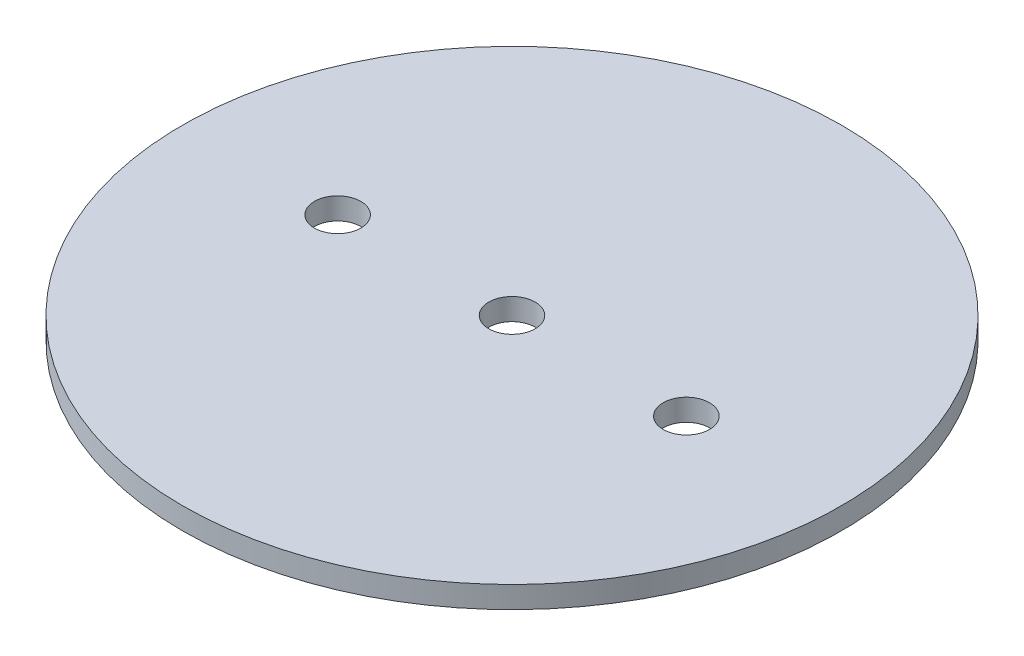
SolidWorks part; units mm, degrees
material "A-Glass Fiber"
ref_plane "Front Plane" through (0, 0, 0) normal (0, 0, 1) x (1, 0, 0)
ref_plane "Top Plane" through (0, 0, 0) normal (0, 1, 0) x (1, 0, 0)
ref_plane "Right Plane" through (0, 0, 0) normal (1, 0, 0) x (0, 0, -1)
sketch "Sketch1" plane through (0, 0, 0) normal (0, 1, 0) x (1, 0, 0)
  circle A0 centre (0, 0) radius 48.006
  dimension "D1" = 96.012
extrude "Boss-Extrude1" add sketch "Sketch1" along normal blind 3.175
sketch "Sketch3" plane through (0, 0, 0) normal (0, -1, 0) x (1, 0, 0)
  line L0 (-25.4, 0) -> (25.4, 0) construction
  point P2 (0, 0)
  dimension "D1" = 25.4
sketch "Sketch4" plane through (0, 0, 0) normal (0, -1, 0) x (-1, 0, 0)
  point P0 (-25.4, 0)
  point P3 (0, 0)
  point P6 (25.4, 0)
hole_wizard "1/4 Clearance Hole1" positions "Sketch4" profile "Sketch5" hole size "1/4" standard "ANSI Inch" end condition through all
sketch "Sketch5" plane through (25.4, 0, 0) normal (1, 0, 0) x (0, 0, -1)
  line L0 (0, 0) -> (0, 3.175)
  line L1 (0, 3.175) -> (3.3782, 3.175)
  line L2 (3.3782, 3.175) -> (3.3782, 0)
  line L5 (3.3782, 0) -> (0, 0)
  line L11 (0, -6.35) -> (0, 107.95) construction
  dimension "Thru Hole Dia." = 6.7564
  dimension "Thru Hole Depth" = 3.175
